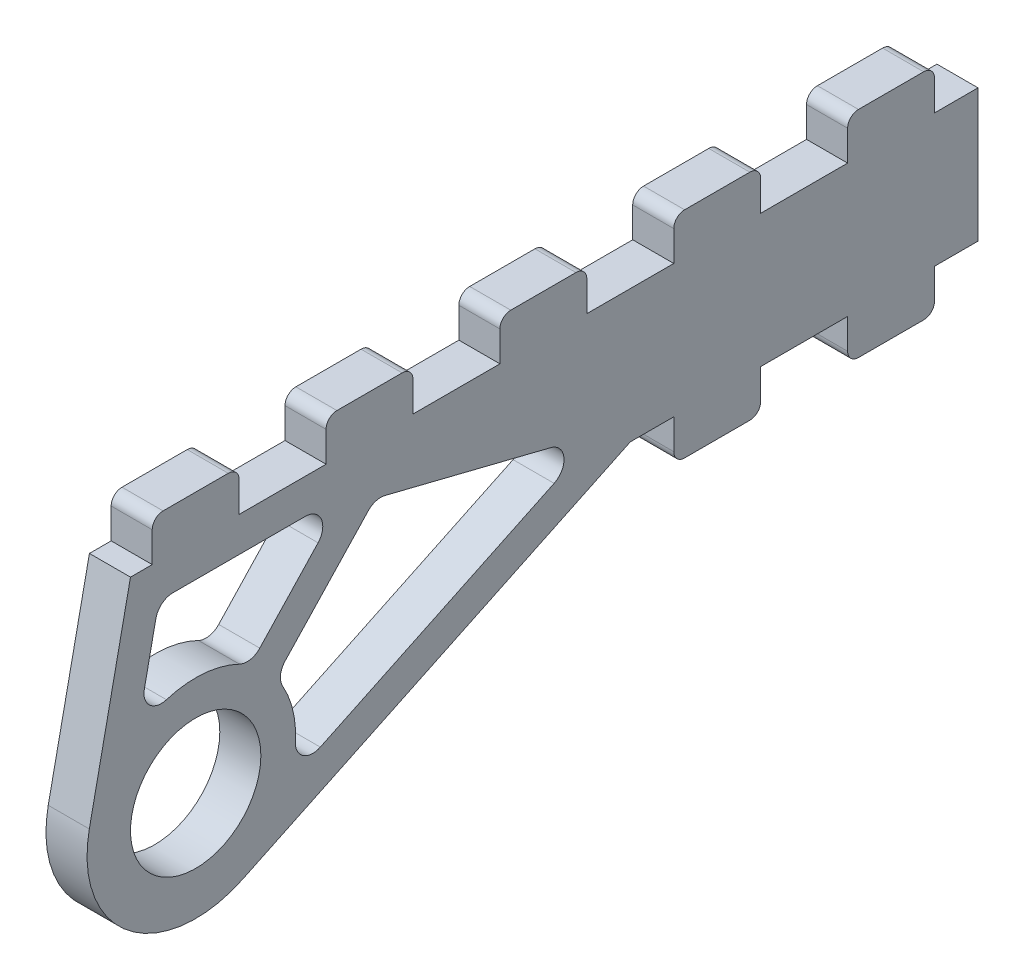
SolidWorks part; units mm, degrees
ref_plane "Front Plane" through (0, 0, 0) normal (0, 0, 1) x (1, 0, 0)
ref_plane "Top Plane" through (0, 0, 0) normal (0, 1, 0) x (1, 0, 0)
ref_plane "Right Plane" through (0, 0, 0) normal (1, 0, 0) x (0, 0, -1)
sketch "Sketch1" plane through (0, 0, 0) normal (1, 0, 0) x (0, 0, -1)
  line L0 (-41.4563, 38.1) -> (38.3452, 38.1) construction
  line L1 (-15.541, 3.2395) -> (-9.525, 32.1)
  line L2 (38.9021, 32.1) -> (-38.9021, 32.1) construction
  line L3 (38.9021, 32.1) -> (38.9021, 38.1) construction
  line L4 (38.9021, 38.1) -> (-38.9021, 38.1) construction
  line L5 (-38.9021, 32.1) -> (-38.9021, 38.1) construction
  line L6 (38.9021, 32.1) -> (-38.9021, 38.1) construction
  line L7 (38.9021, 38.1) -> (-38.9021, 32.1) construction
  line L8 (0, 7.3323) -> (-6.35, 3.6662) construction
  line L9 (-6.35, 3.6662) -> (-6.35, -3.6662) construction
  line L10 (-6.35, -3.6662) -> (0, -7.3323) construction
  line L11 (0, -7.3323) -> (6.35, -3.6662) construction
  line L12 (6.35, -3.6662) -> (6.35, 3.6662) construction
  line L13 (6.35, 3.6662) -> (0, 7.3323) construction
  line L14 (-9.525, 32.1) -> (63.5, 32.1)
  line L15 (0, -15.875) -> (63.5, -15.875)
  line L16 (63.5, -15.875) -> (63.5, 32.1)
  line L18 (157.9971, 6.7) -> (88.9, 6.7) construction
  line L19 (157.9971, 6.7) -> (157.9971, 12.7) construction
  line L20 (157.9971, 12.7) -> (88.9, 12.7) construction
  line L21 (88.9, 6.7) -> (88.9, 12.7) construction
  line L22 (157.9971, 6.7) -> (88.9, 12.7) construction
  line L23 (157.9971, 12.7) -> (88.9, 6.7) construction
  circle A0 centre (0, 0) radius 9.525
  arc A1 (-15.541, 3.2395) -> (0, -15.875) centre (0, 0) ccw
  circle A2 centre (0, 0) radius 25.4 construction
  circle A3 centre (0, 0) radius 6.35 construction
  arc A4 (0, -15.875) -> (-15.541, 3.2395) centre (0, 0) ccw construction
  point P3 (123.4486, 9.7)
  point P7 (0, 35.1)
  point P28 (88.9, 9.7)
  dimension "D1" = 19.05
  dimension "D2" = 6.35
  dimension "D4" = 50.8
  dimension "D3" = 38.1
  dimension "D5" = 6
  dimension "D6" = 12.7
  dimension "D7" = 9.525
  dimension "D8" = 63.5
  dimension "D9" = 25.4
  dimension "D10" = 88.9
extrude "Boss-Extrude1" add sketch "Sketch1" along normal mid plane 6
sketch "Sketch2" plane through (3, 0, 0) normal (1, 0, 0) x (0, 0, -1)
  line L0 (6.8345, -14.3285) -> (63.5, 12.7)
  line L2 (63.5, -15.875) -> (63.5, 32.1) construction
  line L5 (63.5, 12.7) -> (63.5, -15.875)
  line L8 (63.5, -15.875) -> (0, -15.875)
  line L11 (0, -15.875) -> (63.5, -15.875) construction
  line L12 (157.9971, 12.7) -> (88.9, 12.7) construction
  line L22 (0, 0) -> (15.49, 0) construction
  circle A10 centre (0, 0) radius 15.875 construction
  arc A11 (6.8345, -14.3285) -> (0, -15.875) centre (0, 0) cw
  arc A13 (-15.541, 3.2395) -> (0, -15.875) centre (0, 0) ccw construction
extrude "Cut-Extrude1" cut sketch "Sketch2" against normal through all
sketch "Sketch4" plane through (3, 0, 0) normal (1, 0, 0) x (0, 0, -1)
  line L0 (157.9971, 12.7) -> (88.9, 12.7) construction
  line L1 (63.5, 32.1) -> (114.3, 32.1)
  line L2 (63.5, 32.1) -> (63.5, 12.7)
  line L3 (63.5, 12.7) -> (114.3, 12.7)
  line L4 (114.3, 32.1) -> (114.3, 12.7)
  line L5 (88.9, 6.7) -> (88.9, 12.7) construction
  dimension "D1" = 25.4
extrude "Boss-Extrude3" add sketch "Sketch4" against normal up to surface (6 mm away) up to face at (-3, 11.7739, -20.6636)
sketch "Sketch3" plane through (0, 32.1, 0) normal (0, 1, 0) x (1, 0, 0)
  line L0 (3, 114.3) -> (3, -9.525) construction
  line L1 (-3, -6.35) -> (3, -6.35)
  line L2 (-3, -6.35) -> (-3, 6.35)
  line L3 (-3, 6.35) -> (3, 6.35)
  line L4 (3, -6.35) -> (3, 6.35)
  line L5 (-3, -6.35) -> (3, 6.35) construction
  line L6 (-3, 6.35) -> (3, -6.35) construction
  point P0 (0, 0)
  dimension "D1" = 12.7
extrude "Boss-Extrude2" add sketch "Sketch3" along normal blind 6
fillet "Fillet1" radius 1.5875 2 edges at (0, 38.1, -6.35) (0, 38.1, 6.35)
pattern_linear "LPattern1" count 5 spacing 25.4 along (0, 0, -1) of "Boss-Extrude2", "Fillet1"
sketch "Sketch5" plane through (-3, 0, 0) normal (-1, 0, 0) x (0, 0, 1)
  line L0 (-114.3, 12.7) -> (-63.5, 12.7) construction
  line L1 (-69.85, 12.7) -> (-82.55, 12.7)
  line L2 (-69.85, 12.7) -> (-69.85, 6.7)
  line L3 (-69.85, 6.7) -> (-82.55, 6.7)
  line L4 (-82.55, 12.7) -> (-82.55, 6.7)
  line L5 (-69.85, 36.5125) -> (-69.85, 32.1) construction
  line L6 (-82.55, 36.5125) -> (-82.55, 32.1) construction
  dimension "D1" = 6
extrude "Boss-Extrude4" add sketch "Sketch5" against normal up to surface (6 mm away) up to face at (3, 31.7217, -49.7894)
fillet "Fillet2" radius 1.5875 2 edges at (0, 6.7, -69.85) (0, 6.7, -82.55)
pattern_linear "LPattern2" count 2 spacing 25.4 along (0, 0, -1) of "Boss-Extrude4", "Fillet2"
sketch "Sketch6" plane through (3, 0, 0) normal (1, 0, 0) x (0, 0, -1)
  line L0 (-5.3947, 27.02) -> (-10.5678, 2.2029)
  line L1 (4.6474, -9.7434) -> (62.3505, 17.78)
  line L2 (62.3505, 17.78) -> (74.93, 17.78)
  line L3 (74.93, 17.78) -> (74.93, 11.78)
  line L4 (74.93, 11.78) -> (77.47, 11.78)
  line L5 (77.47, 11.78) -> (77.47, 17.78)
  line L6 (77.47, 17.78) -> (100.33, 17.78)
  line L7 (100.33, 17.78) -> (100.33, 11.78)
  line L8 (100.33, 11.78) -> (102.87, 11.78)
  line L9 (102.87, 11.78) -> (102.87, 17.78)
  line L10 (102.87, 17.78) -> (109.22, 17.78)
  line L11 (109.22, 17.78) -> (109.22, 27.02)
  line L12 (109.22, 27.02) -> (102.87, 27.02)
  line L13 (102.87, 27.02) -> (102.87, 33.02)
  line L14 (102.87, 33.02) -> (100.33, 33.02)
  line L15 (100.33, 33.02) -> (100.33, 27.02)
  line L16 (100.33, 27.02) -> (77.47, 27.02)
  line L17 (77.47, 27.02) -> (77.47, 33.02)
  line L18 (77.47, 33.02) -> (74.93, 33.02)
  line L19 (74.93, 33.02) -> (74.93, 27.02)
  line L20 (74.93, 27.02) -> (52.07, 27.02)
  line L21 (52.07, 27.02) -> (52.07, 33.02)
  line L22 (52.07, 33.02) -> (49.53, 33.02)
  line L23 (49.53, 33.02) -> (49.53, 27.02)
  line L24 (49.53, 27.02) -> (26.67, 27.02)
  line L25 (26.67, 27.02) -> (26.67, 33.02)
  line L26 (26.67, 33.02) -> (24.13, 33.02)
  line L27 (24.13, 33.02) -> (24.13, 27.02)
  line L28 (24.13, 27.02) -> (1.27, 27.02)
  line L29 (1.27, 27.02) -> (1.27, 33.02)
  line L30 (1.27, 33.02) -> (-1.27, 33.02)
  line L31 (-1.27, 33.02) -> (-1.27, 27.02)
  line L32 (-1.27, 27.02) -> (-5.3947, 27.02)
  line L33 (95.25, 12.7) -> (95.25, 8.2875)
  line L34 (96.8375, 6.7) -> (106.3625, 6.7)
  line L35 (107.95, 8.2875) -> (107.95, 12.7)
  line L36 (107.95, 12.7) -> (114.3, 12.7)
  line L37 (114.3, 12.7) -> (114.3, 32.1)
  line L38 (114.3, 32.1) -> (107.95, 32.1)
  line L39 (107.95, 32.1) -> (107.95, 36.5125)
  line L40 (106.3625, 38.1) -> (96.8375, 38.1)
  line L41 (95.25, 36.5125) -> (95.25, 32.1)
  line L42 (95.25, 32.1) -> (82.55, 32.1)
  line L43 (82.55, 32.1) -> (82.55, 36.5125)
  line L44 (80.9625, 38.1) -> (71.4375, 38.1)
  line L45 (69.85, 36.5125) -> (69.85, 32.1)
  line L46 (69.85, 32.1) -> (57.15, 32.1)
  line L47 (57.15, 32.1) -> (57.15, 36.5125)
  line L48 (55.5625, 38.1) -> (46.0375, 38.1)
  line L49 (44.45, 36.5125) -> (44.45, 32.1)
  line L50 (44.45, 32.1) -> (31.75, 32.1)
  line L51 (31.75, 32.1) -> (31.75, 36.5125)
  line L52 (30.1625, 38.1) -> (20.6375, 38.1)
  line L53 (19.05, 36.5125) -> (19.05, 32.1)
  line L54 (19.05, 32.1) -> (6.35, 32.1)
  line L55 (6.35, 32.1) -> (6.35, 36.5125)
  line L56 (4.7625, 38.1) -> (-4.7625, 38.1)
  line L57 (-6.35, 36.5125) -> (-6.35, 32.1)
  line L58 (-6.35, 32.1) -> (-9.525, 32.1)
  line L59 (-9.525, 32.1) -> (-15.541, 3.2395)
  line L60 (6.8345, -14.3285) -> (63.5, 12.7)
  line L61 (63.5, 12.7) -> (69.85, 12.7)
  line L62 (69.85, 12.7) -> (69.85, 8.2875)
  line L63 (71.4375, 6.7) -> (80.9625, 6.7)
  line L64 (82.55, 8.2875) -> (82.55, 12.7)
  line L65 (82.55, 12.7) -> (95.25, 12.7)
  line L66 (95.25, 12.7) -> (95.25, 8.2875)
  line L67 (96.8375, 6.7) -> (106.3625, 6.7)
  line L68 (107.95, 8.2875) -> (107.95, 12.7)
  line L69 (107.95, 12.7) -> (114.3, 12.7)
  line L70 (114.3, 12.7) -> (114.3, 32.1)
  line L71 (114.3, 32.1) -> (107.95, 32.1)
  line L72 (107.95, 32.1) -> (107.95, 36.5125)
  line L73 (106.3625, 38.1) -> (96.8375, 38.1)
  line L74 (95.25, 36.5125) -> (95.25, 32.1)
  line L75 (95.25, 32.1) -> (82.55, 32.1)
  line L76 (82.55, 32.1) -> (82.55, 36.5125)
  line L77 (80.9625, 38.1) -> (71.4375, 38.1)
  line L78 (69.85, 36.5125) -> (69.85, 32.1)
  line L79 (69.85, 32.1) -> (57.15, 32.1)
  line L80 (57.15, 32.1) -> (57.15, 36.5125)
  line L81 (55.5625, 38.1) -> (46.0375, 38.1)
  line L82 (44.45, 36.5125) -> (44.45, 32.1)
  line L83 (44.45, 32.1) -> (31.75, 32.1)
  line L84 (31.75, 32.1) -> (31.75, 36.5125)
  line L85 (30.1625, 38.1) -> (20.6375, 38.1)
  line L86 (19.05, 36.5125) -> (19.05, 32.1)
  line L87 (19.05, 32.1) -> (6.35, 32.1)
  line L88 (6.35, 32.1) -> (6.35, 36.5125)
  line L89 (4.7625, 38.1) -> (-4.7625, 38.1)
  line L90 (-6.35, 36.5125) -> (-6.35, 32.1)
  line L91 (-6.35, 32.1) -> (-9.525, 32.1)
  line L92 (-9.525, 32.1) -> (-15.541, 3.2395)
  line L93 (6.8345, -14.3285) -> (63.5, 12.7)
  line L94 (63.5, 12.7) -> (69.85, 12.7)
  line L95 (69.85, 12.7) -> (69.85, 8.2875)
  line L96 (71.4375, 6.7) -> (80.9625, 6.7)
  line L97 (82.55, 8.2875) -> (82.55, 12.7)
  line L98 (82.55, 12.7) -> (95.25, 12.7)
  line L99 (0, 0) -> (25.3883, 27.02) construction
  line L100 (25.3883, 27.02) -> (62.3505, 17.78) construction
  line L101 (1.8511, -1.7393) -> (26.2186, 24.1943)
  line L102 (26.2186, 24.1943) -> (61.7345, 15.3158)
  line L103 (-1.8511, 1.7393) -> (24.5581, 29.8457)
  line L104 (24.5581, 29.8457) -> (62.9665, 20.2442)
  line L105 (-1.27, 27.02) -> (1.27, 27.02)
  circle A0 centre (0, 0) radius 9.525 construction
  circle A1 centre (0, 0) radius 9.525
  arc A2 (-10.5678, 2.2029) -> (4.6474, -9.7434) centre (0, 0) ccw
  arc A3 (74.93, 11.78) -> (74.93, 11.78) centre (74.93, 11.78) ccw
  arc A4 (77.47, 11.78) -> (77.47, 11.78) centre (77.47, 11.78) ccw
  arc A5 (100.33, 11.78) -> (100.33, 11.78) centre (100.33, 11.78) ccw
  arc A6 (102.87, 11.78) -> (102.87, 11.78) centre (102.87, 11.78) ccw
  arc A7 (102.87, 33.02) -> (102.87, 33.02) centre (102.87, 33.02) ccw
  arc A8 (100.33, 33.02) -> (100.33, 33.02) centre (100.33, 33.02) ccw
  arc A9 (77.47, 33.02) -> (77.47, 33.02) centre (77.47, 33.02) ccw
  arc A10 (74.93, 33.02) -> (74.93, 33.02) centre (74.93, 33.02) ccw
  arc A11 (52.07, 33.02) -> (52.07, 33.02) centre (52.07, 33.02) ccw
  arc A12 (49.53, 33.02) -> (49.53, 33.02) centre (49.53, 33.02) ccw
  arc A13 (26.67, 33.02) -> (26.67, 33.02) centre (26.67, 33.02) ccw
  arc A14 (24.13, 33.02) -> (24.13, 33.02) centre (24.13, 33.02) ccw
  arc A15 (95.25, 8.2875) -> (96.8375, 6.7) centre (96.8375, 8.2875) ccw
  arc A16 (106.3625, 6.7) -> (107.95, 8.2875) centre (106.3625, 8.2875) ccw
  arc A17 (107.95, 36.5125) -> (106.3625, 38.1) centre (106.3625, 36.5125) ccw
  arc A18 (96.8375, 38.1) -> (95.25, 36.5125) centre (96.8375, 36.5125) ccw
  arc A19 (82.55, 36.5125) -> (80.9625, 38.1) centre (80.9625, 36.5125) ccw
  arc A20 (71.4375, 38.1) -> (69.85, 36.5125) centre (71.4375, 36.5125) ccw
  arc A21 (57.15, 36.5125) -> (55.5625, 38.1) centre (55.5625, 36.5125) ccw
  arc A22 (46.0375, 38.1) -> (44.45, 36.5125) centre (46.0375, 36.5125) ccw
  arc A23 (31.75, 36.5125) -> (30.1625, 38.1) centre (30.1625, 36.5125) ccw
  arc A24 (20.6375, 38.1) -> (19.05, 36.5125) centre (20.6375, 36.5125) ccw
  arc A25 (6.35, 36.5125) -> (4.7625, 38.1) centre (4.7625, 36.5125) ccw
  arc A26 (-4.7625, 38.1) -> (-6.35, 36.5125) centre (-4.7625, 36.5125) ccw
  arc A27 (-15.541, 3.2395) -> (6.8345, -14.3285) centre (0, 0) ccw
  arc A28 (69.85, 8.2875) -> (71.4375, 6.7) centre (71.4375, 8.2875) ccw
  arc A29 (80.9625, 6.7) -> (82.55, 8.2875) centre (80.9625, 8.2875) ccw
  arc A30 (95.25, 8.2875) -> (96.8375, 6.7) centre (96.8375, 8.2875) ccw
  arc A31 (106.3625, 6.7) -> (107.95, 8.2875) centre (106.3625, 8.2875) ccw
  arc A32 (107.95, 36.5125) -> (106.3625, 38.1) centre (106.3625, 36.5125) ccw
  arc A33 (96.8375, 38.1) -> (95.25, 36.5125) centre (96.8375, 36.5125) ccw
  arc A34 (82.55, 36.5125) -> (80.9625, 38.1) centre (80.9625, 36.5125) ccw
  arc A35 (71.4375, 38.1) -> (69.85, 36.5125) centre (71.4375, 36.5125) ccw
  arc A36 (57.15, 36.5125) -> (55.5625, 38.1) centre (55.5625, 36.5125) ccw
  arc A37 (46.0375, 38.1) -> (44.45, 36.5125) centre (46.0375, 36.5125) ccw
  arc A38 (31.75, 36.5125) -> (30.1625, 38.1) centre (30.1625, 36.5125) ccw
  arc A39 (20.6375, 38.1) -> (19.05, 36.5125) centre (20.6375, 36.5125) ccw
  arc A40 (6.35, 36.5125) -> (4.7625, 38.1) centre (4.7625, 36.5125) ccw
  arc A41 (-4.7625, 38.1) -> (-6.35, 36.5125) centre (-4.7625, 36.5125) ccw
  arc A42 (-15.541, 3.2395) -> (6.8345, -14.3285) centre (0, 0) ccw
  arc A43 (69.85, 8.2875) -> (71.4375, 6.7) centre (71.4375, 8.2875) ccw
  arc A44 (80.9625, 6.7) -> (82.55, 8.2875) centre (80.9625, 8.2875) ccw
  arc A45 (1.27, 33.02) -> (1.27, 33.02) centre (1.27, 33.02) ccw
  arc A46 (-1.27, 33.02) -> (-1.27, 33.02) centre (-1.27, 33.02) ccw
  circle A47 centre (0, 0) radius 14.605
  dimension "D1" = 0
  dimension "D2" = 5.08
  dimension "D3" = 5.08
  dimension "D4" = 2.54
  dimension "D5" = 2.54
extrude "Cut-Extrude2" cut sketch "Sketch6" against normal through all contours A47 L103 L28 L105 L32 L0 | A47 L1 L102 L101 region at (3, 20.8392, -4.7306) region at (3, 11.4157, -30.486)
fillet "Fillet3" radius 2.54 8 edges at (0, 8.7422, -11.6996) (0, 24.1943, -26.2186) (0, 16.0622, -58.749) (0, 11.8332, 8.5604) (0, 27.02, 5.3947) (0, 27.02, -21.903) (0, 12.2208, -7.9974) (0, -5.5082, -13.5265)
